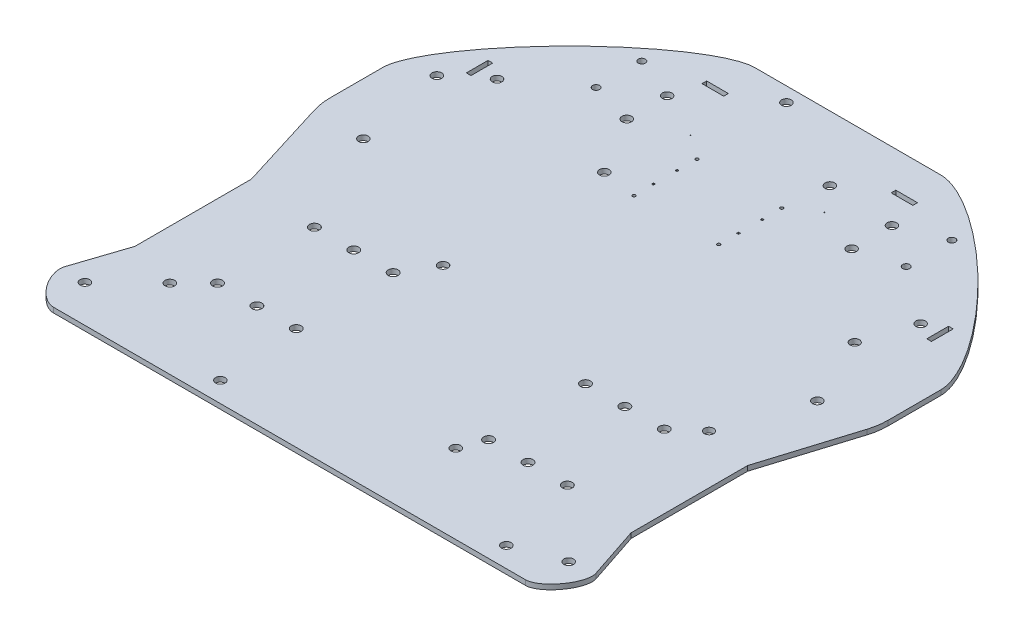
SolidWorks part; units mm, degrees
ref_plane "Front Plane" through (0, 0, 0) normal (0, 0, 1) x (1, 0, 0)
ref_plane "Top Plane" through (0, 0, 0) normal (0, 1, 0) x (1, 0, 0)
ref_plane "Right Plane" through (0, 0, 0) normal (1, 0, 0) x (0, 0, -1)
sketch "Sketch1" plane through (0, 0, 0) normal (0, 1, 0) x (1, 0, 0)
  line L0 (-90, 180) -> (-90, 0) construction
  line L1 (-180, 180) -> (0, 180)
  line L2 (-180, 180) -> (-180, 0)
  line L3 (-180, 0) -> (0, 0)
  line L4 (0, 180) -> (0, 0)
  line L5 (-180, 90) -> (0, 90) construction
  line L6 (-180, 30) -> (0, 30)
  line L7 (-130, 30) -> (-50, 30)
  line L8 (-130, 30) -> (-130, -30)
  line L9 (-130, -30) -> (-50, -30)
  line L10 (-50, 30) -> (-50, -30)
  line L11 (-130, 30) -> (-50, -30) construction
  line L12 (-130, -30) -> (-50, 30) construction
  dimension "D1" = 180
  dimension "D2" = 180
  dimension "D3" = 60
  dimension "D4" = 80
extrude "Boss-Extrude1" add sketch "Sketch1" along normal blind 1.6 contours L10 L3 L8 L9 | L2 L6 L4 L1 | L6 L10 L3 L4 | L8 L6 L2 L3 | L10 L6 L8 L3 region at (-90, 0, -105) region at (-155, 0, -15) region at (-25, 0, -15) region at (-90, 0, -15) region at (-90, 0, 15)
sketch "Sketch2" plane through (0, 1.6, 0) normal (0, 1, 0) x (1, 0, 0)
  line L0 (-180, 30) -> (0, 30)
  line L1 (-180, 180) -> (-180, 0) construction
  line L2 (0, 180) -> (0, 0) construction
  line L3 (-180, 180) -> (0, 180) construction
  line L4 (-90, 180) -> (-90, -30) construction
  line L5 (-130, -30) -> (-50, -30) construction
  dimension "D1" = 150
sketch "Sketch3" plane through (0, 1.6, 0) normal (0, 1, 0) x (1, 0, 0)
  line L0 (-180, 122) -> (0, 122)
  line L1 (-180, 180) -> (-180, 0) construction
  line L2 (0, 180) -> (0, 0) construction
  line L3 (-180, 30) -> (0, 30) construction
  dimension "D1" = 92
sketch "Sketch5" plane through (0, 1.6, 0) normal (0, 1, 0) x (1, 0, 0)
  line L0 (-114, 180) -> (-114, -30)
  line L1 (-180, 180) -> (0, 180) construction
  line L2 (-130, -30) -> (-50, -30) construction
  line L3 (-90, 180) -> (-90, -30) construction
  dimension "D1" = 24
fillet "Fillet1" radius 60 2 edges at (0, 0.8, -180) (-180, 0.8, -180) conic rho 0.2
sketch "Sketch6" plane through (0, 1.6, 0) normal (0, 1, 0) x (1, 0, 0)
  line L0 (-50, 0) -> (-130, 0)
  line L1 (-130, 0) -> (-130, -30)
  line L2 (-130, -30) -> (-50, -30)
  line L3 (-50, -30) -> (-50, 0)
  line L4 (-180, 0) -> (-170, 30.1113)
  line L5 (-170, 30.1113) -> (-170, 67.7113)
  line L6 (-170, 67.7113) -> (-180, 100)
  line L7 (-180, 120) -> (-180, 0) construction
  line L8 (-90, 180) -> (-90, -30) construction
  line L10 (-90, 180) -> (-90, 0) construction
  line L11 (0, 0) -> (-10, 30.1113)
  line L12 (-10, 30.1113) -> (-10, 67.7113)
  line L13 (-10, 67.7113) -> (0, 100)
  line M3 (0, 0) -> (0, 120)
  line M7 (-180, 120) -> (-180, 0)
  line M9 (-130, 0) -> (-130, -30)
  line M10 (-130, -30) -> (-50, -30)
  line M11 (-50, -30) -> (-50, 0)
  dimension "D1" = 37.6
  dimension "D2" = 80
  dimension "D3" = 100
extrude "Cut-Extrude1" cut sketch "Sketch6" against normal blind 10 contours L0 M11 M9 M10 | L5 L6 L4 M7 | L13 L12 L11 M3 region at (-90, 1.6, 15) region at (-175.7558, 1.6, -49.5379) region at (-4.2442, 1.6, -49.5379)
fillet "Fillet2" radius 10 2 edges at (-180, 0.8, 0) (0, 0.8, 0) conic rho 0.25
fillet "Fillet3" radius 20 2 edges at (-180, 0.8, -100) (0, 0.8, -100)
sketch "Sketch8" plane through (0, 1.6, 0) normal (0, 1, 0) x (1, 0, 0)
  line L1 (-63, 168.5) -> (-56, 168.5)
  line L2 (-63, 168.5) -> (-63, 167)
  line L3 (-63, 167) -> (-56, 167)
  line L4 (-56, 168.5) -> (-56, 167)
  line L5 (-117, 168.5) -> (-124, 168.5)
  line L6 (-117, 168.5) -> (-117, 167)
  line L7 (-117, 167) -> (-124, 167)
  line L8 (-124, 168.5) -> (-124, 167)
  line L9 (-165, 139) -> (-163.5, 139)
  line L10 (-165, 139) -> (-165, 132)
  line L11 (-165, 132) -> (-163.5, 132)
  line L12 (-163.5, 139) -> (-163.5, 132)
  line L13 (-16.5, 139) -> (-15, 139)
  line L14 (-16.5, 139) -> (-16.5, 132)
  line L15 (-16.5, 132) -> (-15, 132)
  line L16 (-15, 139) -> (-15, 132)
  circle A4 centre (-105.105, 175.3311) radius 1.55
  circle A5 centre (-74.9002, 159.1312) radius 1.55
  circle A8 centre (-115, 74.5) radius 1.55
  circle A9 centre (-115, 126.5) radius 1.55
  circle A11 centre (-146.4125, 64.417) radius 1.5875
  circle A12 centre (-133.7125, 64.417) radius 1.5875
  circle A13 centre (-121.0125, 64.417) radius 1.5875
  circle A14 centre (-146.4125, 33.175) radius 1.5875
  circle A15 centre (-133.7125, 33.175) radius 1.5875
  circle A16 centre (-121.0125, 33.175) radius 1.5875
  circle A17 centre (-58.9875, 64.417) radius 1.5875
  circle A18 centre (-46.2875, 64.417) radius 1.5875
  circle A19 centre (-33.5875, 64.417) radius 1.5875
  circle A20 centre (-33.5875, 33.175) radius 1.5875
  circle A21 centre (-46.2875, 33.175) radius 1.5875
  circle A22 centre (-58.9875, 33.175) radius 1.5875
  circle A23 centre (-61.9, 25.5) radius 1.55
  circle A24 centre (-26.6, 6.5) radius 1.55
  circle A25 centre (-118.8, 6.5) radius 1.55
  circle A26 centre (-154.1, 25.5) radius 1.55
  circle A27 centre (-27.14, 119.392) radius 1.5
  circle A28 centre (-25.87, 71.132) radius 1.5
  circle A29 centre (-169, 126.5) radius 1.55
  circle A30 centre (-126.25, 145) radius 1.55
  circle A31 centre (-53.75, 145) radius 1.55
  circle A32 centre (-168, 12) radius 1.55
  circle A33 centre (-12, 12) radius 1.55
  dimension "D3" = 3.1
  dimension "D4" = 3.1
  dimension "D5" = 3.1
  dimension "D6" = 3.1
  dimension "D7" = 3.1
  dimension "D8" = 3.175
  dimension "D9" = 3.175
  dimension "D10" = 3.175
  dimension "D11" = 3.175
  dimension "D12" = 3.175
  dimension "D13" = 3.175
  dimension "D14" = 3.1
  dimension "D15" = 3.1
  dimension "D16" = 3.1
  dimension "D17" = 3.1
  dimension "D18" = 3.175
  dimension "D19" = 3.175
  dimension "D20" = 3.175
  dimension "D21" = 3.175
  dimension "D22" = 3.175
  dimension "D23" = 3.175
  dimension "D24" = 3
  dimension "D25" = 3
  dimension "D26" = 3.1
  dimension "D27" = 3.1
  dimension "D28" = 3.1
  dimension "D29" = 3.1
extrude "Cut-Extrude2" cut sketch "Sketch8" against normal up to next (1.6 mm away)
sketch "Sketch9" plane through (0, 0, 0) normal (0, -1, 0) x (1, 0, 0)
  line L1 (-68.18, -150.89) -> (-68.42, -150.89)
  line L2 (-68.18, -150.89) -> (-68.18, -150.65)
  line L3 (-68.18, -150.65) -> (-68.42, -150.65)
  line L4 (-68.42, -150.89) -> (-68.42, -150.65)
  line L5 (-111.36, -150.89) -> (-111.6, -150.89)
  line L6 (-111.36, -150.89) -> (-111.36, -150.65)
  line L7 (-111.36, -150.65) -> (-111.6, -150.65)
  line L8 (-111.6, -150.89) -> (-111.6, -150.65)
  line L9 (-76.01, -139.0625) -> (-76.645, -139.0625)
  line L10 (-76.01, -139.0625) -> (-76.01, -138.4275)
  line L11 (-76.01, -138.4275) -> (-76.645, -138.4275)
  line L12 (-76.645, -139.0625) -> (-76.645, -138.4275)
  line L13 (-76.01, -131.4425) -> (-76.645, -131.4425)
  line L14 (-76.01, -131.4425) -> (-76.01, -130.8075)
  line L15 (-76.01, -130.8075) -> (-76.645, -130.8075)
  line L16 (-76.645, -131.4425) -> (-76.645, -130.8075)
  line L17 (-103.47, -139.0625) -> (-104.105, -139.0625)
  line L18 (-103.47, -139.0625) -> (-103.47, -138.4275)
  line L19 (-103.47, -138.4275) -> (-104.105, -138.4275)
  line L20 (-104.105, -139.0625) -> (-104.105, -138.4275)
  line L21 (-103.47, -131.4425) -> (-104.105, -131.4425)
  line L22 (-103.47, -131.4425) -> (-103.47, -130.8075)
  line L23 (-103.47, -130.8075) -> (-104.105, -130.8075)
  line L24 (-104.105, -131.4425) -> (-104.105, -130.8075)
  circle A0 centre (-163.2, -97) radius 1.55
  circle A1 centre (-158.3, -135.2) radius 1.55
  circle A2 centre (-126.25, -158) radius 1.55
  circle A3 centre (-53.75, -158) radius 1.55
  circle A4 centre (-21.7, -135.2) radius 1.55
  circle A5 centre (-16.8, -97) radius 1.55
  circle A6 centre (-76.405, -124.775) radius 0.5
  circle A7 centre (-103.71, -145.095) radius 0.5
  circle A8 centre (-76.405, -145.095) radius 0.5
  circle A9 centre (-103.71, -124.775) radius 0.5
  circle A10 centre (-140, -148.857) radius 1.143
  circle A11 centre (-140, -163.589) radius 1.143
  circle A12 centre (-40, -148.857) radius 1.143
  circle A13 centre (-40, -163.589) radius 1.143
  dimension "D1" = 3.1
  dimension "D2" = 3.1
  dimension "D3" = 3.1
  dimension "D4" = 3.1
  dimension "D5" = 3.1
  dimension "D6" = 3.1
  dimension "D7" = 1
  dimension "D8" = 1
  dimension "D9" = 1
  dimension "D10" = 1
  dimension "D11" = 2.286
  dimension "D12" = 2.286
  dimension "D13" = 2.286
  dimension "D14" = 2.286
extrude "Cut-Extrude3" cut sketch "Sketch9" against normal up to next
